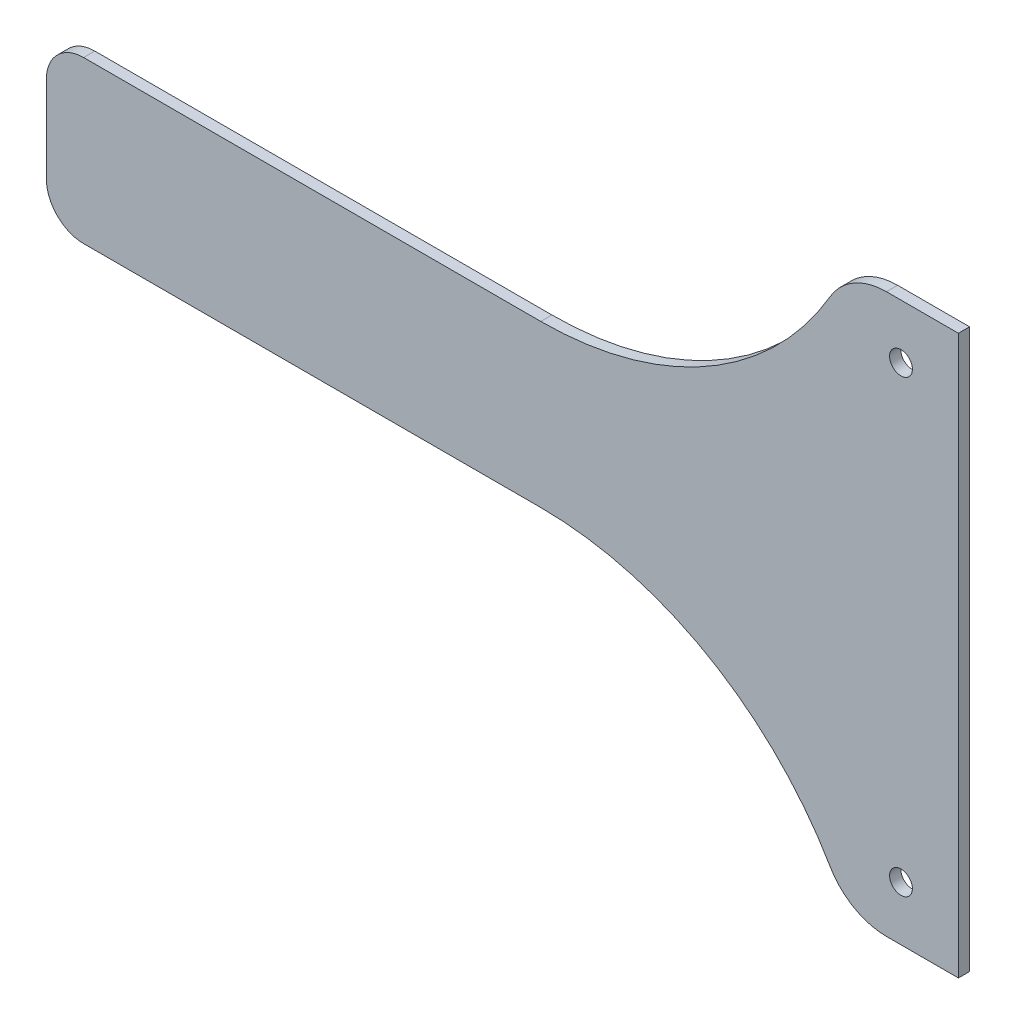
SolidWorks part; units mm, degrees
ref_plane "Front Plane" through (0, 0, 0) normal (0, 0, 1) x (1, 0, 0)
ref_plane "Top Plane" through (0, 0, 0) normal (0, 1, 0) x (1, 0, 0)
ref_plane "Right Plane" through (0, 0, 0) normal (1, 0, 0) x (0, 0, -1)
sketch "Sketch1" plane through (0, 0, 0) normal (0, 0, 1) x (1, 0, 0)
  line L0 (0, 49.0982) -> (0, 76.2)
  line L1 (0, 0) -> (15.24, 0)
  line L2 (0, 0) -> (0, 27.1018)
  line L3 (0, 76.2) -> (15.24, 76.2)
  line L4 (15.24, 0) -> (15.24, 76.2)
  line L5 (-109.22, 27.1018) -> (0, 27.1018)
  line L6 (-109.22, 27.1018) -> (-109.22, 49.0982)
  line L7 (-109.22, 49.0982) -> (0, 49.0982)
  circle A0 centre (7.4041, 68.7959) radius 1.5558
  circle A1 centre (7.4041, 7.4041) radius 1.5557
  dimension "D5" = 3.1115
  dimension "D1" = 76.2
  dimension "D2" = 15.24
  dimension "D3" = 21.9964
  dimension "D4" = 109.22
  dimension "D6" = 7.4041
  dimension "D7" = 7.4041
extrude "Boss-Extrude1" add sketch "Sketch1" along normal blind 1.524
fillet "Fillet1" radius 5.08 2 edges at (-109.22, 27.1018, 0.762) (-109.22, 49.0982, 0.762)
fillet "Fillet2" radius 45.72 2 edges at (0, 27.1018, 0.762) (0, 49.0982, 0.762)
fillet "Fillet3" radius 8.89 2 edges at (0, 0, 0.762) (0, 76.2, 0.762)
